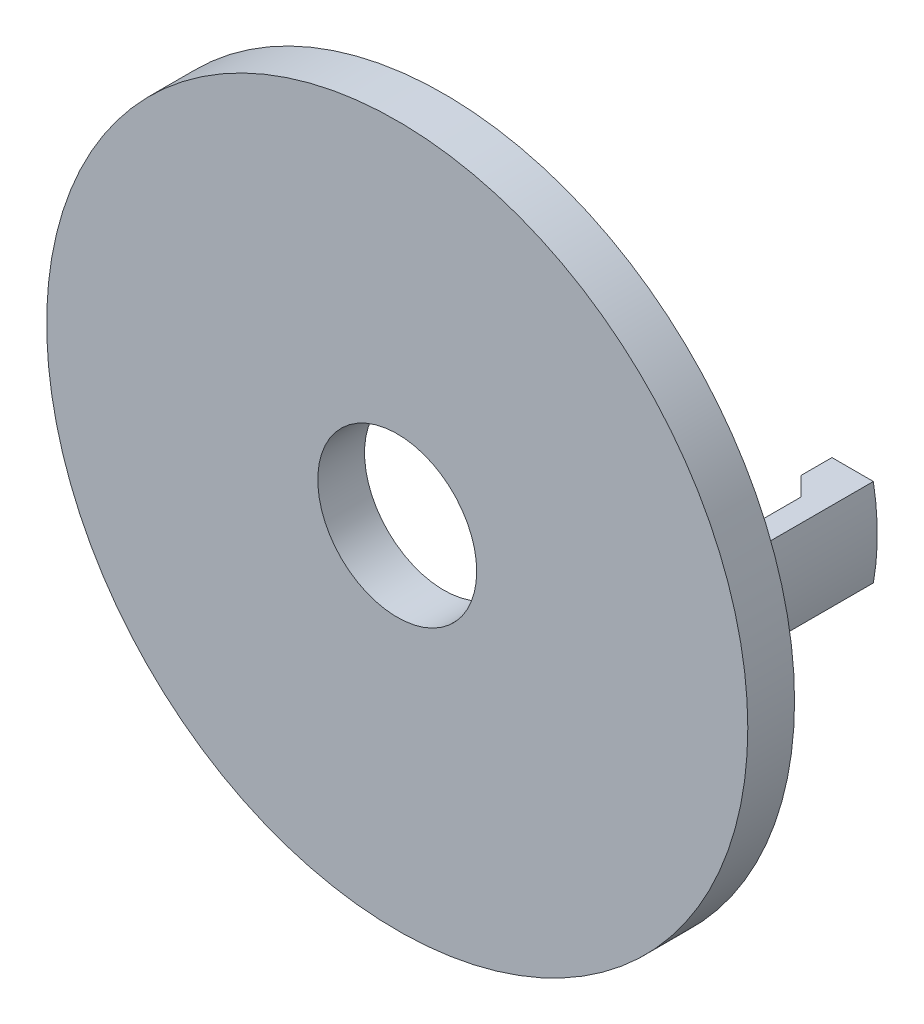
SolidWorks part; units mm, degrees
ref_plane "Front" through (0, 0, 0) normal (0, 0, 1) x (1, 0, 0)
ref_plane "Top" through (0, 0, 0) normal (0, 1, 0) x (1, 0, 0)
ref_plane "Right" through (0, 0, 0) normal (1, 0, 0) x (0, 0, -1)
sketch "Sketch1" plane through (0, 0, 0) normal (0, 0, 1) x (1, 0, 0)
  circle A0 centre (0, 0) radius 26.5
  circle A1 centre (0, 0) radius 37.5
  dimension "D1" = 53
  dimension "D2" = 75
sketch "Sketch4" plane through (0, 0, 0) normal (0, 0, 1) x (1, 0, 0)
  circle A0 centre (0, 0) radius 37.5
  dimension "D1" = 75
extrude "Boss-Extrude2" add sketch "Sketch4" along normal blind 5
sketch "Sketch5" plane through (0, 0, 5) normal (0, 0, 1) x (1, 0, 0)
  circle A0 centre (0, 0) radius 8.5
  dimension "D1" = 17
extrude "Cut-Extrude1" cut sketch "Sketch5" against normal through all
sketch "Sketch6" plane through (0, 0, 0) normal (0, 1, 0) x (1, 0, 0)
  line L0 (23.5, 0) -> (26.5, 0) construction
  line L1 (26.5, 0) -> (26.5, 20) construction
  line L2 (26.5, 0) -> (20.7121, 0)
  line L3 (26.5, 20) -> (21.5, 20) construction
  line L4 (21.5, 20) -> (21.5, 16.5) construction
  line L5 (21.5, 16.5) -> (23.5, 14.5) construction
  line L6 (23.5, 14.5) -> (23.5, 0) construction
  line L7 (23.65, 14.5621) -> (23.65, 2.9379)
  line L8 (23.5, 3) -> (20.5, 0) construction
  line L9 (23.65, 14.5621) -> (21.65, 16.5621)
  line L10 (21.65, 16.5621) -> (21.65, 19.85)
  line L11 (21.65, 19.85) -> (26.5, 19.85)
  line L12 (26.5, 19.85) -> (26.5, 0)
  line L13 (20.5, 0) -> (23.5, 0) construction
  line L14 (23.65, 2.9379) -> (20.7121, 0)
  dimension "D1" = 135
  dimension "D2" = 3
  dimension "D3" = 5
  dimension "D4" = 20
  dimension "D5" = 3.5
  dimension "D6" = 0.3
  dimension "D7" = 0.3
  dimension "D8" = 0.3
  dimension "D9" = 0.3
  dimension "D10" = 3
  dimension "D11" = 3
  dimension "D12" = 0.3
extrude "Boss-Extrude3" add sketch "Sketch6" along normal blind 4.7 and the other way blind 4.7
mirror "Mirror1" about plane through (0, 0, 0) normal (1, 0, 0) of "Boss-Extrude3"
extrude "Cut-Extrude2" cut sketch "Sketch1" against normal through all
equation "\"female_make_room\"=0.3"
equation "\"D6@Sketch6\"=\"female_make_room\""
equation "\"D8@Sketch6\"=\"female_make_room\""
equation "\"D7@Sketch6\"=\"female_make_room\""
equation "\"D9@Sketch6\"=\"female_make_room\""
equation "\"D12@Sketch6\"=\"female_make_room\""
